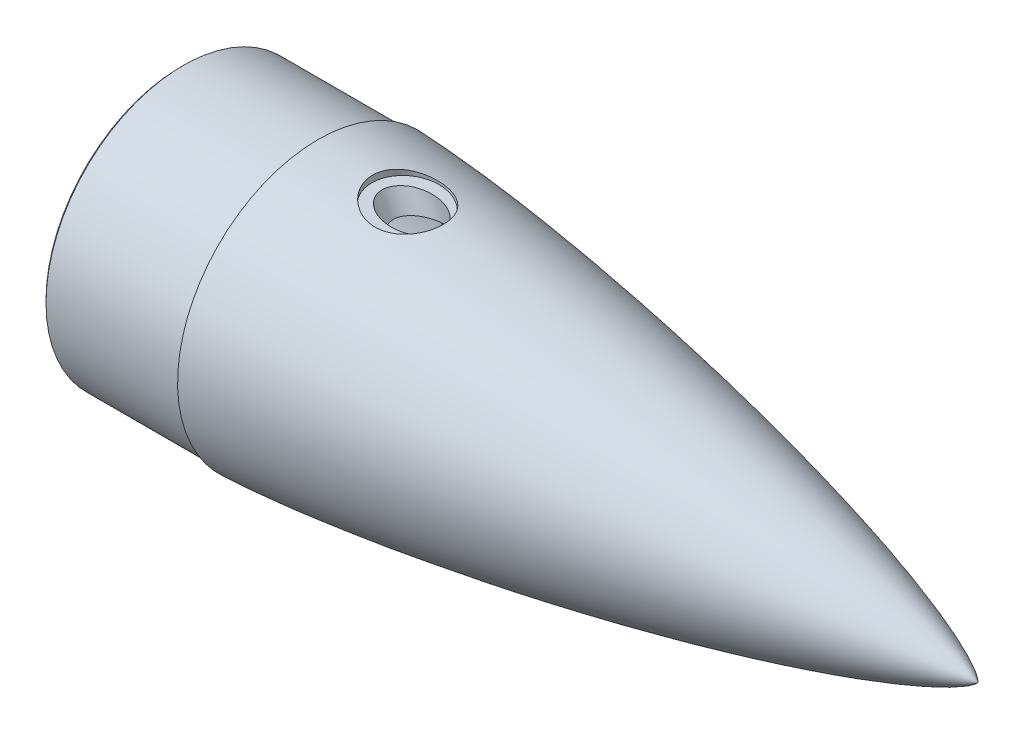
SolidWorks part; units mm, degrees
material "Plain Carbon Steel"
ref_plane "Front Plane" through (0, 0, 0) normal (0, 0, 1) x (1, 0, 0)
ref_plane "Top Plane" through (0, 0, 0) normal (0, 1, 0) x (1, 0, 0)
ref_plane "Right Plane" through (0, 0, 0) normal (1, 0, 0) x (0, 0, -1)
ref_axis "Axis1" through (444.767, 0, 0) along (-1, 0, 0)
sketch "Sketch10" plane through (0, 0, 0) normal (0, 0, 1) x (1, 0, 0)
  line L1 (-1.0327, 0) -> (486.9547, 0) construction
  line L2 (11.1125, 81.9998) -> (11.1125, 67.4998)
  line L3 (11.1125, 81.9998) -> (-84.6045, 81.9998)
  line L4 (408.9673, 0) -> (368.9673, 0)
  line L5 (-84.6045, 81.9998) -> (-84.6045, 84.9998)
  line L6 (-84.6045, 84.9998) -> (0.3953, 84.9998)
  line L7 (0.3953, 84.9998) -> (0.3953, 86.9998)
  line L8 (11.1125, 67.4998) -> (129.3045, 67.4998)
  line L9 (433.6458, 0) -> (-109.2831, 0) construction
  spline S0 degree 4 poles (408.9673, 0) (408.9649, 0.0135) (408.958, 0.0399) (408.9365, 0.0905) (408.8922, 0.1741) (408.8263, 0.2756) (408.7217, 0.4158) (408.5611, 0.6051) (408.3056, 0.8724) (407.8697, 1.2753) (407.121, 1.8851) (405.8038, 2.8259) (403.4624, 4.2872) (399.3253, 6.5318) (392.4811, 9.7589) (380.6621, 14.628) (363.6372, 20.7117) (342.2152, 27.4765) (317.4285, 34.4976) (291.8793, 41.1048) (266.2105, 47.229) (240.4455, 52.9334) (214.5989, 58.2554) (188.6809, 63.2176) (165.9462, 67.2533) (146.422, 70.4938) (130.1279, 73.0449) (117.0786, 74.9942) (104.0155, 76.8485) (92.5733, 78.3845) (82.7571, 79.6356) (74.5713, 80.6322) (68.0193, 81.4008) (61.4637, 82.1394) (54.9047, 82.8464) (48.3422, 83.5199) (41.7761, 84.1578) (36.0275, 84.6822) (31.0979, 85.1052) (26.9883, 85.4387) (23.6997, 85.6932) (20.0858, 85.9584) (16.7199, 86.189) (13.6021, 86.387) (10.7327, 86.5546) (8.4366, 86.6787) (6.14, 86.7922) (4.1299, 86.8793) (2.4065, 86.9446) (1.2573, 86.979) (0.6827, 86.9949) (0.3953, 86.9998) knots 0 0 0 0 0 0.00013 0.00026 0.00052 0.0009 0.00128 0.001925 0.002882 0.004418 0.006927 0.011111 0.018279 0.030673 0.051704 0.083102 0.139909 0.202703 0.265496 0.32829 0.391083 0.453877 0.516671 0.579464 0.642258 0.673655 0.705051 0.736448 0.767845 0.799242 0.81494 0.830639 0.846337 0.862036 0.877734 0.893432 0.909131 0.924829 0.932678 0.940527 0.948377 0.956226 0.967169 0.972641 0.978113 0.983585 0.989056 0.994528 0.997264 1 1 1 1 1 construction
  spline S1 degree 4 poles (408.9673, 0) (408.9649, 0.0135) (408.958, 0.0399) (408.9365, 0.0905) (408.8922, 0.1741) (408.8263, 0.2756) (408.7217, 0.4158) (408.5611, 0.6051) (408.3056, 0.8724) (407.8697, 1.2753) (407.121, 1.8851) (405.8038, 2.8259) (403.4624, 4.2872) (399.3253, 6.5318) (392.4811, 9.7589) (380.6621, 14.628) (363.6372, 20.7117) (342.2152, 27.4765) (317.4285, 34.4976) (291.8793, 41.1048) (266.2105, 47.229) (240.4455, 52.9334) (214.5989, 58.2554) (188.6809, 63.2176) (165.9462, 67.2533) (146.422, 70.4938) (130.1279, 73.0449) (117.0786, 74.9942) (104.0155, 76.8485) (92.5733, 78.3845) (82.7571, 79.6356) (74.5713, 80.6322) (68.0193, 81.4008) (61.4637, 82.1394) (54.9047, 82.8464) (48.3422, 83.5199) (41.7761, 84.1578) (36.0275, 84.6822) (31.0979, 85.1052) (26.9883, 85.4387) (23.6997, 85.6932) (20.0858, 85.9584) (16.7199, 86.189) (13.6021, 86.387) (10.7327, 86.5546) (8.4366, 86.6787) (6.14, 86.7922) (4.1299, 86.8793) (2.4065, 86.9446) (1.2573, 86.979) (0.6827, 86.9949) (0.3953, 86.9998) knots 0 0 0 0 0 0.00013 0.00026 0.00052 0.0009 0.00128 0.001925 0.002882 0.004418 0.006927 0.011111 0.018279 0.030673 0.051704 0.083102 0.139909 0.202703 0.265496 0.32829 0.391083 0.453877 0.516671 0.579464 0.642258 0.673655 0.705051 0.736448 0.767845 0.799242 0.81494 0.830639 0.846337 0.862036 0.877734 0.893432 0.909131 0.924829 0.932678 0.940527 0.948377 0.956226 0.967169 0.972641 0.978113 0.983585 0.989056 0.994528 0.997264 1 1 1 1 1
  spline S2 degree 4 poles (368.9673, 0) (368.9653, 0.0123) (368.9594, 0.0365) (368.9406, 0.083) (368.9023, 0.1587) (368.8455, 0.2503) (368.7557, 0.3766) (368.6167, 0.5484) (368.3929, 0.7936) (368.0087, 1.1649) (367.3447, 1.7299) (366.1761, 2.6016) (364.0928, 3.96) (360.426, 6.0407) (354.4022, 9.0183) (344.043, 13.5077) (329.152, 19.1285) (310.4252, 25.3986) (288.7413, 31.9337) (266.3785, 38.1061) (243.9014, 43.8469) (221.332, 49.212) (198.684, 54.2345) (175.9669, 58.9343) (156.0346, 62.7717) (138.9133, 65.8645) (124.6221, 68.3077) (113.1754, 70.1797) (101.7151, 71.9664) (91.6754, 73.4517) (83.0615, 74.6659) (75.8775, 75.6363) (70.1269, 76.3867) (64.3728, 77.1101) (58.6152, 77.8049) (52.854, 78.4695) (47.0892, 79.1019) (42.0417, 79.6247) (37.7129, 80.0488) (34.1039, 80.385) (31.2157, 80.6428) (28.0648, 80.911) (24.6507, 81.1843) (21.4654, 81.4195) (18.5093, 81.6177) (16.0448, 81.767) (14.3191, 81.8612) (12.8395, 81.9336) (11.8527, 81.9739) (11.3593, 81.993) (11.1125, 81.9998) knots 0 0 0 0 0 0.000135 0.00027 0.00054 0.00092 0.001299 0.001947 0.002931 0.004512 0.007081 0.01138 0.018708 0.031424 0.052705 0.084103 0.14091 0.203703 0.266497 0.329291 0.392084 0.454878 0.517672 0.580465 0.643259 0.674656 0.706052 0.737449 0.768846 0.800243 0.815941 0.831639 0.847338 0.863036 0.878735 0.894433 0.910132 0.92583 0.933679 0.941528 0.949378 0.957227 0.96792 0.978613 0.98396 0.989307 0.994653 0.997327 1 1 1 1 1 construction
  spline S3 degree 4 poles (368.9673, 0) (368.9653, 0.0123) (368.9594, 0.0365) (368.9406, 0.083) (368.9023, 0.1587) (368.8455, 0.2503) (368.7557, 0.3766) (368.6167, 0.5484) (368.3929, 0.7936) (368.0087, 1.1649) (367.3447, 1.7299) (366.1761, 2.6016) (364.0928, 3.96) (360.426, 6.0407) (354.4022, 9.0183) (344.043, 13.5077) (329.152, 19.1285) (310.4252, 25.3986) (288.7413, 31.9337) (266.3785, 38.1061) (243.9014, 43.8469) (221.332, 49.212) (198.684, 54.2345) (175.9669, 58.9343) (156.0346, 62.7717) (141.5091, 65.3956) (132.6794, 66.9245) (129.5628, 67.4559) (129.3045, 67.4998) knots 0 0 0 0 0 0.000135 0.00027 0.00054 0.00092 0.001299 0.001947 0.002931 0.004512 0.007081 0.01138 0.018708 0.031424 0.052705 0.084103 0.14091 0.203703 0.266497 0.329291 0.392084 0.454878 0.517672 0.580465 0.643259 0.674656 0.677492 0.677492 0.677492 0.677492 0.677492
  dimension "D1" = 86.9998
  dimension "D2" = 3
  dimension "D3" = 410
  dimension "D4" = 84.9998
  dimension "D5" = 370
  dimension "D6" = 84.9998
  dimension "D7" = 19.5
  dimension "D8" = 118.192
revolve "Revolve1" add sketch "Sketch10" angle 360 about axis through (444.767, 0, 0) along (-1, 0, 0)
chamfer "Chamfer1" distance 1.5 angle 45 1 edges at (-84.6045, 0, -84.9998)
ref_plane "Plane2" through (11.1125, 0, 0) normal (-1, 0, 0) x (0, 0, 1)
sketch "Sketch12" plane through (11.1125, 0, 0) normal (-1, 0, 0) x (0, 0, 1)
  circle A4 centre (-73.1248, 0) radius 4
  circle A5 centre (-36.5624, 63.328) radius 4
  circle A6 centre (36.5624, 63.328) radius 4
  circle A7 centre (73.1248, 0) radius 4
  circle A8 centre (36.5624, -63.328) radius 4
  circle A9 centre (-36.5624, -63.328) radius 4
  point P17 (-50.2998, -44.6412)
  point P25 (0, 0)
  dimension "D1" = 6
hole_wizard "Tap Drill for #1 Helicoil1" positions "Sketch17" profile "Sketch18" hole size "#1-64" standard "ANSI Inch"
sketch "Sketch17" plane through (11.1125, 0, 0) normal (-1, 0, 0) x (0, 0, 1)
  point P0 (-36.5624, 63.328)
sketch "Sketch18" plane through (11.1125, 63.328, -36.5624) normal (0, 1, 0) x (0, 0, 1)
  line L0 (0, 0) -> (0, 9.53)
  line L1 (0, 9.53) -> (3.3782, 9.53)
  line L2 (3.3782, 9.53) -> (3.3782, 0)
  line L5 (3.3782, 0) -> (0, 0)
  line L10 (0, 9.53) -> (-3.3782, 9.53) construction
  line L11 (0, -6.35) -> (0, 107.95) construction
  dimension "Hole Dia." = 6.7564
  dimension "Hole Depth" = 9.53
  dimension "Drill Angle" = 180
pattern_circular "CirPattern1" count 6 over 360 about axis through (11.1125, 0, 0) along (1, 0, 0) of "Tap Drill for #1 Helicoil1"
ref_plane "Plane3" through (0, 85, 0) normal (0, 1, 0) x (1, 0, 0)
sketch "Sketch20" plane through (0, 85, 0) normal (0, 1, 0) x (1, 0, 0)
  line L0 (433.6458, 0) -> (-109.2831, 0) construction
  line L1 (24.7702, 25) -> (64.7702, 25)
  line L2 (24.7702, 25) -> (24.7702, -15)
  line L3 (24.7702, -15) -> (64.7702, -15)
  line L4 (64.7702, 25) -> (64.7702, -15)
  line L5 (24.7702, 25) -> (64.7702, -15) construction
  line L6 (24.7702, -15) -> (64.7702, 25) construction
  point P4 (44.7702, 5)
  dimension "D1" = 40
  dimension "D2" = 15
  dimension "D3" = 40
extrude "Cut-Extrude3" [suppressed] cut sketch "Sketch20" along normal blind 12
sketch "Sketch22" plane through (0, 85, 0) normal (0, 1, 0) x (1, 0, 0)
  circle A0 centre (32, 6) radius 7.5
  dimension "D1" = 15
extrude "Cut-Extrude4" [suppressed] cut sketch "Sketch22" along normal through all
sketch "Sketch24" plane through (0, 85, 0) normal (0, 1, 0) x (1, 0, 0)
  line L0 (38.1988, 66.2764) -> (38.1988, 16.8548) construction
ref_plane "Plane4" through (-27.2564, 47.2094, 0) normal (-0.5, 0.866, 0) x (0, 0, 1)
sketch "Sketch26" plane through (-27.2564, 47.2094, 0) normal (-0.5, 0.866, 0) x (0, 0, 1)
  circle A0 centre (0, 89.5256) radius 15
extrude "Cut-Extrude5" cut sketch "Sketch26" against normal blind 50
extrude "Cut-Extrude6" cut sketch "Sketch26<2>" along normal blind 50
sketch "Sketch26<2>" plane through (-27.2564, 47.2094, 0) normal (-0.5, 0.866, 0) x (0, 0, 1) same geometry as "Sketch26"
ref_plane "Plane5" through (9.2536, 88.0423, 0) normal (0.1045, 0.9945, 0) x (0, 0, 1)
sketch "Sketch30" plane through (9.2536, 88.0423, 0) normal (0.1045, 0.9945, 0) x (0, 0, 1)
  line L0 (0, 442.3305) -> (0, -97.6242) construction
  circle A0 centre (0, 47.1511) radius 22
extrude "Cut-Extrude10" cut sketch "Sketch30" against normal blind 5
equation "\"TubeDiameter\" = 6.250in"
